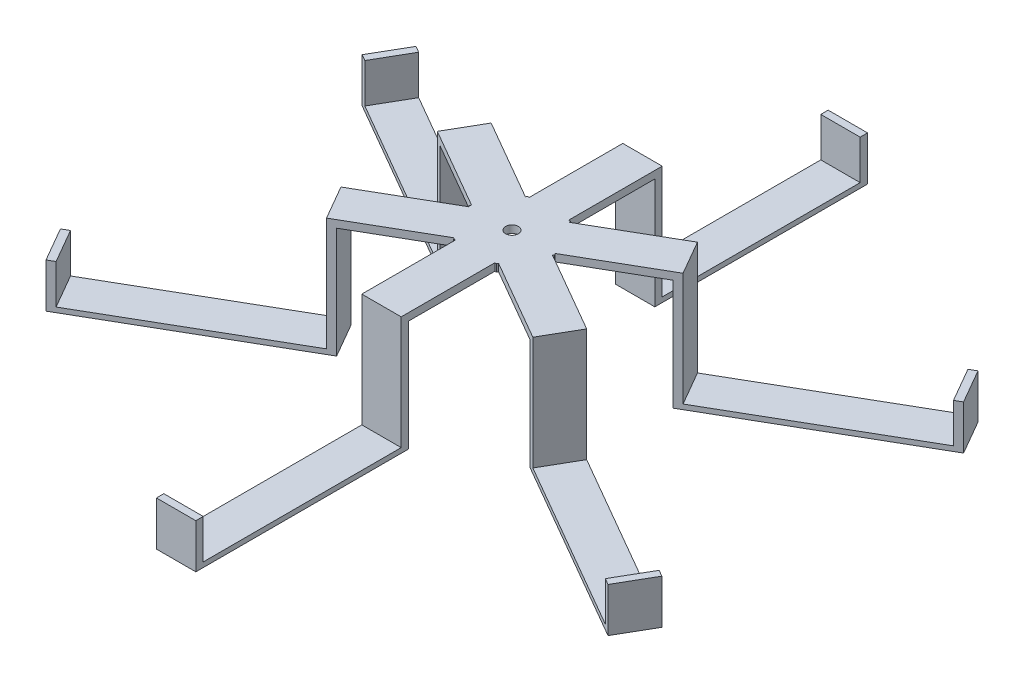
SolidWorks part; units mm, degrees
ref_plane "前视基准面" through (0, 0, 0) normal (0, 0, 1) x (1, 0, 0)
ref_plane "上视基准面" through (0, 0, 0) normal (0, 1, 0) x (1, 0, 0)
ref_plane "右视基准面" through (0, 0, 0) normal (1, 0, 0) x (0, 0, -1)
other "Configuration Table"
sketch "草图1" plane through (0, 0, 0) normal (0, 1, 0) x (1, 0, 0)
  line L1 (8.6603, 15) -> (-8.6603, 15)
  line L2 (-8.6603, 15) -> (-17.3205, 0)
  line L3 (-17.3205, 0) -> (-8.6603, -15)
  line L4 (-8.6603, -15) -> (8.6603, -15)
  line L5 (8.6603, -15) -> (17.3205, 0)
  line L6 (17.3205, 0) -> (8.6603, 15)
  circle A0 centre (0, 0) radius 15 construction
  circle A1 centre (0, 0) radius 2.6
  dimension "D1" = 30
  dimension "D2" = 5.2
extrude "凸台-拉伸1" add sketch "草图1" along normal blind 3
sketch "草图2" plane through (0, 0, 0) normal (1, 0, 0) x (0, 0, -1)
  line L0 (0, 3) -> (0, 0) construction
  line L1 (15, 0) -> (50, 0)
  line L2 (15, 0) -> (15, 3)
  line L3 (15, 3) -> (53, 3)
  line L6 (53, 3) -> (53, -43)
  line L8 (50, 0) -> (50, -45)
  line L9 (50, -45) -> (136.4, -45)
  line L11 (53, -43) -> (133.4, -43)
  line L13 (0, 3) -> (15, 3) construction
  line L16 (136.4, -45) -> (136.4, -27)
  line L17 (136.4, -27) -> (133.4, -27)
  line L18 (133.4, -43) -> (133.4, -27)
  point P16 (133.4, -28)
  point P17 (133.4, -43)
  point P18 (133.4, -40.1069)
  point P19 (136.4, -42.7699)
  point P20 (136.6193, -45)
  dimension "D1" = 3
  dimension "D2" = 2
  dimension "D3" = 50
  dimension "D4" = 45
  dimension "D5" = 86.4
  dimension "D6" = 18
  dimension "D7" = 3
extrude "凸台-拉伸2" add sketch "草图2" along normal blind 8 and the other way blind 8
pattern_circular "阵列(圆周)1" count 6 over 360 about axis through (0, 3, 0) along (0, 1, 0) of "凸台-拉伸2"
